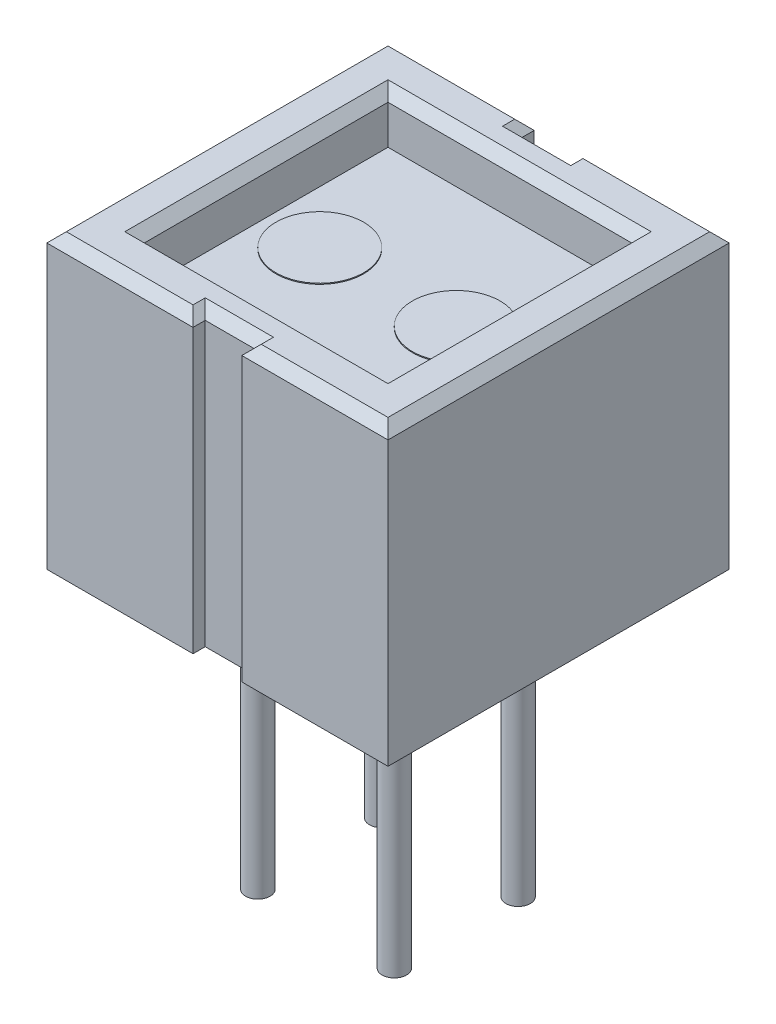
SolidWorks part; units mm, degrees
ref_plane "Alzado" through (0, 0, 0) normal (0, 0, 1) x (1, 0, 0)
ref_plane "Planta" through (0, 0, 0) normal (0, 1, 0) x (1, 0, 0)
ref_plane "Vista lateral" through (0, 0, 0) normal (1, 0, 0) x (0, 0, -1)
sketch "Croquis1" plane through (0, 0, 0) normal (0, 1, 0) x (1, 0, 0)
  line L0 (-0.5, 3.5) -> (-3.5, 3.5)
  line L1 (3.5, -3.5) -> (0.5, -3.5)
  line L2 (3.5, -3.5) -> (3.5, 3.5)
  line L3 (3.5, 3.5) -> (0.5, 3.5)
  line L4 (-3.5, -3.5) -> (-3.5, 3.5)
  line L5 (3.5, -3.5) -> (-3.5, 3.5) construction
  line L6 (3.5, 3.5) -> (-3.5, -3.5) construction
  line L7 (0.5, 3.25) -> (-0.5, 3.25)
  line L8 (0.5, 3.25) -> (0.5, 3.5)
  line L9 (-0.5, -3.5) -> (-3.5, -3.5)
  line L10 (-0.5, 3.25) -> (-0.5, 3.5)
  line L14 (0.5, -3.5) -> (0.5, -3.25)
  line L15 (0.5, -3.25) -> (-0.5, -3.25)
  line L16 (-0.5, -3.5) -> (-0.5, -3.25)
  point P0 (0, 0)
  point P6 (0, 3.5)
  point P11 (0, -3.5)
  dimension "D1" = 7
  dimension "D2" = 7
  dimension "D3" = 1
extrude "Extruir1" add sketch "Croquis1" along normal blind 6
sketch "Croquis2" plane through (0, 6, 0) normal (0, 1, 0) x (-1, 0, 0)
  line L1 (-2.5, 2.5) -> (2.5, 2.5)
  line L2 (-2.5, 2.5) -> (-2.5, -2.5)
  line L3 (-2.5, -2.5) -> (2.5, -2.5)
  line L4 (2.5, 2.5) -> (2.5, -2.5)
  line L5 (-2.5, 2.5) -> (2.5, -2.5) construction
  line L6 (-2.5, -2.5) -> (2.5, 2.5) construction
  point P0 (0, 0)
  dimension "D1" = 5
  dimension "D2" = 5
extrude "Extruir2" cut sketch "Croquis2" against normal blind 1
sketch "Croquis3" plane through (0, 5, 0) normal (0, 1, 0) x (-1, 0, 0)
  line L0 (0, 0) -> (0, -0.7994) construction
  circle A0 centre (1.4, 0) radius 0.9
  dimension "D1" = 1.8
  dimension "D3" = 1.4
extrude "Extruir3" add sketch "Croquis3" along normal blind 0.02
sketch "Croquis7" plane through (0, 5, 0) normal (0, 1, 0) x (-1, 0, 0)
  line L0 (0, 0) -> (0, 0.8865) construction
  circle A0 centre (-1.4, 0) radius 0.9
  dimension "D1" = 1.8
  dimension "D2" = 1.4
extrude "Extruir7" add sketch "Croquis7" along normal blind 0.02
sketch "Croquis9" plane through (0, 0, 0) normal (0, -1, 0) x (1, 0, 0)
  line L0 (-3.5, -3.5) -> (-3.5, 3.5) construction
  line L1 (-2.75, 2.75) -> (2.75, 2.75)
  line L2 (-2.75, 2.75) -> (-2.75, -2.75)
  line L3 (-2.75, -2.75) -> (2.75, -2.75)
  line L4 (2.75, 2.75) -> (2.75, -2.75)
  line L5 (-2.75, 2.75) -> (2.75, -2.75) construction
  line L6 (-2.75, -2.75) -> (2.75, 2.75) construction
  line L7 (3.5, -3.5) -> (0.5, -3.5) construction
  point P0 (0, 0)
  dimension "D1" = 0.75
  dimension "D2" = 0.75
extrude "Extruir8" cut sketch "Croquis9" against normal blind 0.25
sketch "Croquis10" plane through (0, 0.25, 0) normal (0, -1, 0) x (1, 0, 0)
  line L0 (2.75, 0) -> (-2.75, 0) construction
  line L1 (2.75, -2.75) -> (2.75, 2.75) construction
  line L2 (-2.75, 2.75) -> (-2.75, -2.75) construction
  line L3 (0, -2.75) -> (0, 2.75) construction
  line L4 (-2.75, -2.75) -> (2.75, -2.75) construction
  line L5 (2.75, 2.75) -> (-2.75, 2.75) construction
  circle A0 centre (-1.4, 1.27) radius 0.25
  circle A1 centre (1.4, 1.27) radius 0.25
  circle A2 centre (1.4, -1.27) radius 0.25
  circle A3 centre (-1.4, -1.27) radius 0.25
  dimension "D1" = 1.4
  dimension "D3" = 0.5
  dimension "D2" = 1.27
extrude "Extruir9" add sketch "Croquis10" along normal blind 6
fillet "Redondeo2" radius 0.25 4 edges at (0, 0.25, -2.75) (-2.75, 0.25, 0) (0, 0.25, 2.75) (2.75, 0.25, 0)
chamfer "Chaflán1" distance 0.2 angle 45 16 edges at (0, 6, 2.5) (2.5, 6, 0) (0, 6, -2.5) (-2.5, 6, 0) (-2, 6, -3.5) (-0.5, 6, -3.375) (0, 6, -3.25) (0.5, 6, -3.375) (2, 6, -3.5) (3.5, 6, 0) (2, 6, 3.5) (0.5, 6, 3.375) (0, 6, 3.25) (-0.5, 6, 3.375) (-2, 6, 3.5) (-3.5, 6, 0)
sketch "Croquis11" plane through (-3.5, 0, 0) normal (-1, 0, 0) x (0, 0, 1)
  text T0 "CNY 70" font "Verdana" height 0.75
wrap "Envolver1" sketch "Croquis11" wrap type scribe source sketch "Croquis11" face at (-3.5, 2.9, 0)
